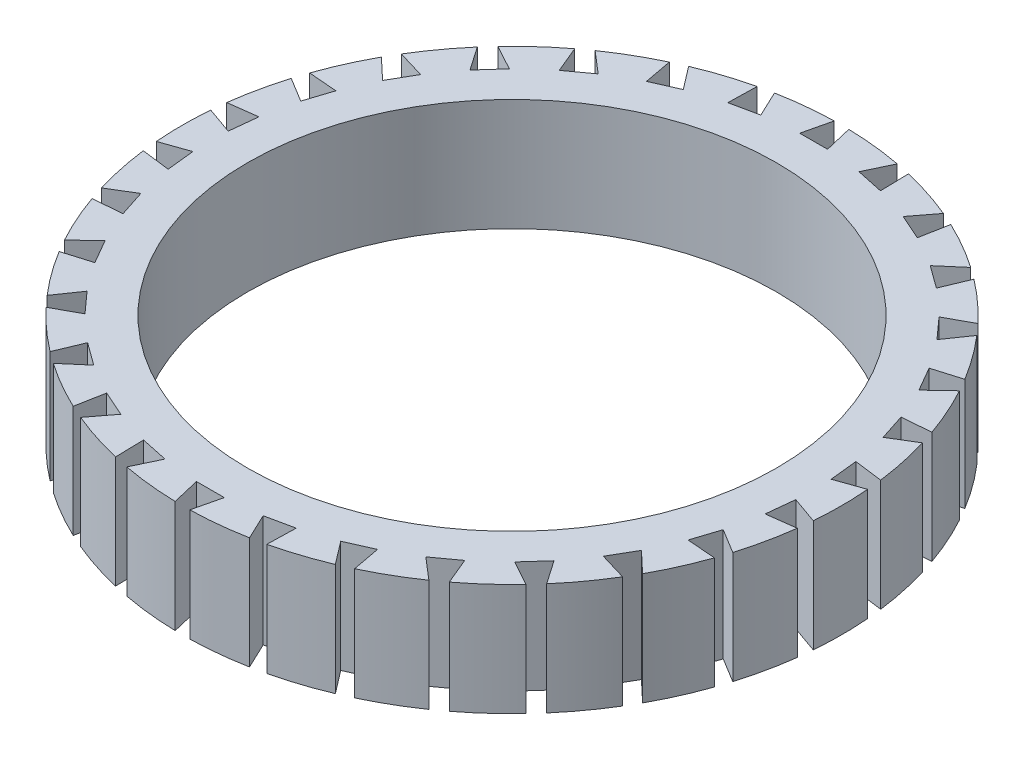
SolidWorks part; units mm, degrees
ref_plane "Front Plane" through (0, 0, 0) normal (0, 0, 1) x (1, 0, 0)
ref_plane "Top Plane" through (0, 0, 0) normal (0, 1, 0) x (1, 0, 0)
ref_plane "Right Plane" through (0, 0, 0) normal (1, 0, 0) x (0, 0, -1)
sketch "Sketch1" plane through (0, 0, 0) normal (0, 1, 0) x (1, 0, 0)
  circle A0 centre (0, 0) radius 16.2
  circle A1 centre (0, 0) radius 13
  dimension "D1" = 3.2
  dimension "D2" = 26
extrude "Boss-Extrude1" add sketch "Sketch1" along normal blind 5.5
sketch "Sketch2" plane through (0, 0, 0) normal (0, 1, 0) x (1, 0, 0)
  line L0 (0, 16.2) -> (0, 0) construction
  line L1 (0.6847, 14.8247) -> (-0.6847, 14.8247)
  line L2 (-0.6847, 14.8247) -> (-0.359, 16.196)
  line L3 (-0.359, 16.196) -> (-0.359, 18.0528)
  line L4 (-0.359, 18.0528) -> (0.359, 18.0528)
  line L5 (0.359, 16.196) -> (0.359, 18.0528)
  line L6 (0.6847, 14.8247) -> (0.359, 16.196)
  circle A0 centre (0, 0) radius 16.2 construction
  point P5 (-0.6779, 16.1858)
  point P11 (0, 18.0528)
  point P13 (0, 14.8247)
  point P14 (-1.0103, 14.7074)
  point P15 (-0.359, 16.196)
  point P16 (-0.6847, 14.8247)
extrude "Cut-Extrude1" cut sketch "Sketch2" along normal through all
pattern_circular "CirPattern1" count 30 over 360 about axis through (0, 5.5, 0) along (0, -1, 0) of "Cut-Extrude1"
